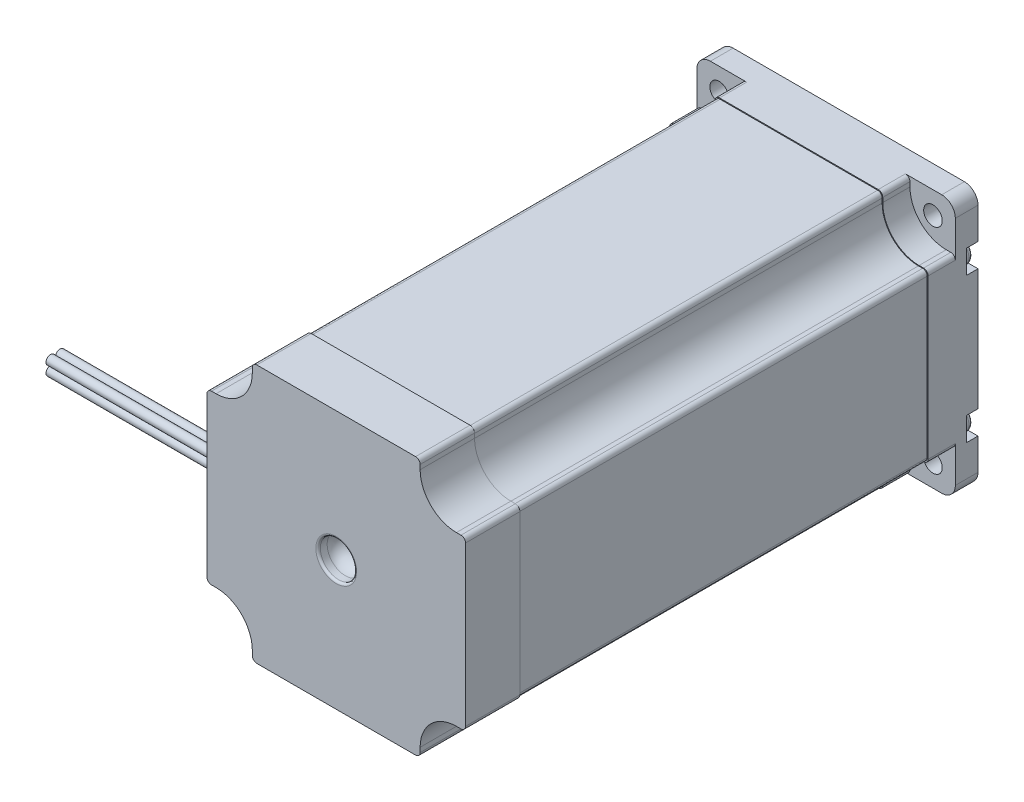
SolidWorks part; units mm, degrees
ref_plane "Front Plane" through (0, 0, 0) normal (0, 0, 1) x (1, 0, 0)
ref_plane "Top Plane" through (0, 0, 0) normal (0, 1, 0) x (1, 0, 0)
ref_plane "Right Plane" through (0, 0, 0) normal (1, 0, 0) x (0, 0, -1)
sketch "Sketch1" plane through (0, 0, 0) normal (0, 0, 1) x (1, 0, 0)
  line L0 (-28.5, 57) -> (-28.5, 0) construction
  line L1 (-3, 0) -> (-54, 0)
  line L2 (0, 3) -> (0, 54)
  line L3 (-3, 57) -> (-54, 57)
  line L4 (-57, 3) -> (-57, 54)
  line L5 (-28.5, 0) -> (-57, 28.5) construction
  line L6 (-57, 28.5) -> (0, 28.5) construction
  circle A0 centre (-52.07, 52.07) radius 2.05
  circle A1 centre (-4.93, 52.07) radius 2.05
  circle A2 centre (-4.93, 4.93) radius 2.05
  circle A3 centre (-52.07, 4.93) radius 2.05
  arc A4 (-3, 0) -> (0, 3) centre (-3, 3) ccw
  arc A5 (-57, 3) -> (-54, 0) centre (-54, 3) ccw
  arc A6 (-3, 57) -> (0, 54) centre (-3, 54) cw
  arc A7 (-57, 54) -> (-54, 57) centre (-54, 54) cw
  point P19 (0, 0)
  point P24 (0, 57)
  point P27 (-57, 57)
  dimension "D3" = 47.14
  dimension "D4" = 47.14
  dimension "D5" = 4.1
  dimension "D6" = 3
  dimension "D1" = 57
  dimension "D2" = 57
extrude "Boss-Extrude1" add sketch "Sketch1" along normal blind 113
sketch "Sketch2" plane through (0, 0, 113) normal (0, 0, 1) x (1, 0, 0)
  line L0 (-47, 60.0294) -> (-47, 47)
  line L1 (-47, 47) -> (-64.0408, 47)
  line L2 (-64.0408, 47) -> (-64.0408, 10)
  line L3 (-64.0408, 10) -> (-47, 10)
  line L4 (-47, 10) -> (-47, -4.5394)
  line L5 (-47, -4.5394) -> (-10, -4.5394)
  line L6 (-10, -4.5394) -> (-10, 10)
  line L7 (-10, 10) -> (8.5456, 10)
  line L8 (8.5456, 10) -> (8.5456, 47)
  line L9 (8.5456, 47) -> (-10, 47)
  line L10 (-10, 47) -> (-10, 60.0294)
  line L11 (-10, 60.0294) -> (-47, 60.0294)
  line L12 (-80.8243, 69.6678) -> (-80.8243, -15.5364)
  line L13 (-80.8243, -15.5364) -> (13.1348, -15.5364)
  line L14 (13.1348, -15.5364) -> (13.1348, 68.1044)
  line L15 (13.1348, 68.1044) -> (-80.8243, 69.6678)
  line L16 (-28.5, 57) -> (-28.5, 0) construction
  line L17 (-3, 57) -> (-54, 57) construction
  line L18 (-54, 0) -> (-3, 0) construction
  line L19 (-28.5, 0) -> (-57, 28.5) construction
  line L20 (-57, 54) -> (-57, 3) construction
  line L21 (-57, 28.5) -> (0, 28.5) construction
  line L22 (0, 3) -> (0, 54) construction
  dimension "D1" = 10
  dimension "D2" = 10
  dimension "D3" = 10
  dimension "D4" = 10
extrude "Cut-Extrude1" cut sketch "Sketch2" against normal blind 108 contours L15 L12 L13 L14 | L11 L0 L1 L2 L3 L4 L5 L6 L7 L8 L9 L10
fillet "Fillet1" radius 8 4 edges at (-10, 10, 59) (-47, 10, 59) (-47, 47, 59) (-10, 47, 59)
fillet "Fillet2" radius 1 8 edges at (-57, 47, 59) (-47, 57, 59) (-10, 57, 59) (0, 47, 59) (0, 10, 59) (-10, 0, 59) (-47, 0, 59) (-57, 10, 59)
ref_plane "Plane4" through (0, 0, 101) normal (0, 0, 1) x (1, 0, 0)
sketch "Sketch3" plane through (0, 0, 101) normal (0, 0, 1) x (1, 0, 0)
  line L0 (-45.8671, 56.8) -> (-11.1329, 56.8)
  line L1 (-10.1329, 55.8) -> (-10.1329, 54.8506)
  line L2 (-2.1329, 46.8506) -> (-1.2, 46.8506)
  line L3 (-0.2, 45.8506) -> (-0.2, 11.1822)
  line L4 (-1.2, 10.1822) -> (-2.0826, 10.1822)
  line L5 (-10.0826, 2.1822) -> (-10.0826, 1.2)
  line L6 (-11.0826, 0.2) -> (-45.9174, 0.2)
  line L7 (-28.5, 0) -> (-28.5, 57) construction
  line L8 (-46, 0) -> (-11, 0) construction
  line L9 (-11, 57) -> (-46, 57) construction
  line L10 (0, 11) -> (0, 46) construction
  line L11 (-10, 1) -> (-10, 2) construction
  line L12 (-46.9174, 2.1822) -> (-46.9174, 1.2)
  line L13 (-55.8, 10.1822) -> (-54.9174, 10.1822)
  line L14 (-56.8, 45.8506) -> (-56.8, 11.1822)
  line L15 (-54.8671, 46.8506) -> (-55.8, 46.8506)
  line L16 (-46.8671, 55.8) -> (-46.8671, 54.8506)
  line L18 (-64.6847, 62.0406) -> (11.9413, 62.0406)
  line L19 (-64.6847, 62.0406) -> (-64.6847, -12.0593)
  line L20 (-64.6847, -12.0593) -> (11.9413, -12.0593)
  line L21 (11.9413, 62.0406) -> (11.9413, -12.0593)
  arc A0 (-10.0826, 2.1822) -> (-2.0826, 10.1822) centre (-2.0826, 2.1822) cw
  arc A1 (-10.1329, 54.8506) -> (-2.1329, 46.8506) centre (-2.1329, 54.8506) ccw
  arc A2 (-11.1329, 56.8) -> (-10.1329, 55.8) centre (-11.1329, 55.8) cw
  arc A3 (-1.2, 46.8506) -> (-0.2, 45.8506) centre (-1.2, 45.8506) cw
  arc A4 (-1.2, 10.1822) -> (-0.2, 11.1822) centre (-1.2, 11.1822) ccw
  arc A5 (-11.0826, 0.2) -> (-10.0826, 1.2) centre (-11.0826, 1.2) ccw
  arc A6 (-10, 55) -> (-2, 47) centre (-2, 55) ccw construction
  arc A7 (-2, 10) -> (-10, 2) centre (-2, 2) ccw construction
  arc A8 (-45.9174, 0.2) -> (-46.9174, 1.2) centre (-45.9174, 1.2) cw
  arc A9 (-55.8, 10.1822) -> (-56.8, 11.1822) centre (-55.8, 11.1822) cw
  arc A10 (-55.8, 46.8506) -> (-56.8, 45.8506) centre (-55.8, 45.8506) ccw
  arc A11 (-45.8671, 56.8) -> (-46.8671, 55.8) centre (-45.8671, 55.8) ccw
  arc A12 (-46.8671, 54.8506) -> (-54.8671, 46.8506) centre (-54.8671, 54.8506) cw
  arc A13 (-46.9174, 2.1822) -> (-54.9174, 10.1822) centre (-54.9174, 2.1822) ccw
  point P8 (-28.5, 56.8)
  point P56 (-28.5, 0.2)
  dimension "D1" = 8
  dimension "D2" = 1
  dimension "D5" = 0.2
  dimension "D7" = 0.2
  dimension "D3" = 0.2
  dimension "D4" = 0.2
  dimension "D6" = 0.2
  dimension "D8" = 0.0826
extrude "Cut-Extrude2" cut sketch "Sketch3" against normal blind 90
sketch "Sketch4" plane through (0, 0, 0) normal (0, 0, -1) x (-1, 0, 0)
  line L0 (28.5, 57) -> (28.5, 0) construction
  line L1 (3, 57) -> (54, 57) construction
  line L2 (54, 0) -> (3, 0) construction
  circle A0 centre (28.5, 28.5) radius 19.05
  dimension "D1" = 38.1
extrude "Boss-Extrude2" add sketch "Sketch4" along normal blind 1.6
sketch "Sketch5" plane through (0, 0, -1.6) normal (0, 0, -1) x (-1, 0, 0)
  circle A0 centre (28.5, 28.5) radius 4
  dimension "D1" = 8
extrude "Boss-Extrude3" add sketch "Sketch5" along normal blind 22.4
sketch "Sketch6" plane through (0, 0, -24) normal (0, 0, -1) x (-1, 0, 0)
  line L0 (20.6729, 24.5) -> (38.159, 24.5) construction
  line L1 (21.9219, 34.9968) -> (35.9108, 34.9968)
  line L2 (21.9219, 34.9968) -> (21.9219, 32)
  line L3 (21.9219, 32) -> (35.9108, 32)
  line L4 (35.9108, 34.9968) -> (35.9108, 32)
  line L5 (54, 0) -> (3, 0) construction
  circle A0 centre (28.5, 28.5) radius 4 construction
  dimension "D1" = 7.5
extrude "Cut-Extrude3" cut sketch "Sketch6" against normal blind 20
sketch "Sketch7" plane through (-57, 0, 0) normal (-1, 0, 0) x (0, 0, 1)
  line L0 (113, 28.5) -> (70.7902, 28.5) construction
  line L1 (113, 46) -> (113, 11) construction
  circle A1 centre (105.3906, 29.7507) radius 1
  circle A2 centre (107.4906, 29.7507) radius 1
  circle A3 centre (107.4906, 27.6507) radius 1
  circle A4 centre (105.3906, 27.6507) radius 1
  dimension "D1" = 2.1
  dimension "D2" = 2
  dimension "D5" = 2.1
  dimension "D3" = 2
  dimension "D4" = 2
extrude "Boss-Extrude4" add sketch "Sketch7" along normal blind 40
fillet "Fillet3" radius 0.5 1 edges at (-47.55, 28.5, -1.6)
sketch "Sketch8" plane through (0, 0, 0) normal (0, 0, -1) x (-1, 0, 0)
  line L0 (28.5, 57) -> (28.5, 0) construction
  line L1 (3, 57) -> (54, 57) construction
  line L2 (54, 0) -> (3, 0) construction
  line L3 (28.5, 0) -> (0, 28.5) construction
  line L4 (0, 3) -> (0, 54) construction
  line L5 (0, 28.5) -> (57, 28.5) construction
  line L6 (57, 54) -> (57, 3) construction
  line L7 (3, 47.07) -> (-1.6146, 47.07)
  line L8 (-1.6146, 47.07) -> (-1.6146, 41.87)
  line L9 (-1.6146, 41.87) -> (3, 41.87)
  line L10 (-1.6146, 15.13) -> (3, 15.13)
  line L11 (-1.6146, 9.93) -> (-1.6146, 15.13)
  line L12 (3, 9.93) -> (-1.6146, 9.93)
  line L13 (58.6146, 9.93) -> (58.6146, 15.13)
  line L14 (54, 9.93) -> (58.6146, 9.93)
  line L15 (58.6146, 15.13) -> (54, 15.13)
  line L16 (58.6146, 41.87) -> (54, 41.87)
  line L17 (58.6146, 47.07) -> (58.6146, 41.87)
  line L18 (54, 47.07) -> (58.6146, 47.07)
  arc A0 (3, 41.87) -> (3, 47.07) centre (3, 44.47) ccw
  arc A1 (3, 15.13) -> (3, 9.93) centre (3, 12.53) cw
  arc A2 (54, 15.13) -> (54, 9.93) centre (54, 12.53) ccw
  arc A3 (54, 41.87) -> (54, 47.07) centre (54, 44.47) cw
  circle A4 centre (4.93, 52.07) radius 2.05 construction
  dimension "D1" = 5.2
  dimension "D2" = 3
  dimension "D3" = 5
extrude "Cut-Extrude4" cut sketch "Sketch8" against normal blind 2.5
sketch "Sketch9" plane through (0, 0, 2.5) normal (0, 0, -1) x (-1, 0, 0)
  line L0 (28.5, 57) -> (28.5, 17.6387) construction
  line L1 (3, 57) -> (54, 57) construction
  line L2 (28.5, 17.6387) -> (0, 28.5) construction
  line L3 (0, 15.13) -> (0, 41.87) construction
  line L4 (0, 28.5) -> (41.5102, 28.5) construction
  circle A0 centre (3, 44.47) radius 2.5
  circle A1 centre (54, 44.47) radius 2.5
  circle A2 centre (54, 12.53) radius 2.5
  circle A3 centre (3, 12.53) radius 2.5
  dimension "D1" = 5
extrude "Boss-Extrude5" add sketch "Sketch9" along normal blind 2 separate body
fillet "Fillet4" radius 1 2 edges at (-5.5, 44.47, 0.5) (-5.5, 44.47, 2.5)
fillet "Fillet5" radius 1 2 edges at (-0.5, 12.53, 2.5) (-0.5, 12.53, 0.5)
fillet "Fillet6" radius 1 2 edges at (-56.5, 12.53, 2.5) (-56.5, 12.53, 0.5)
fillet "Fillet7" radius 1 2 edges at (-51.5, 44.47, 2.5) (-51.5, 44.47, 0.5)
sketch "Sketch10" plane through (0, 0, 0.5) normal (0, 0, -1) x (-1, 0, 0)
  line L0 (3, 45.97) -> (3, 42.97) construction
  line L1 (3, 42.97) -> (1.5, 44.47) construction
  line L2 (1.5, 44.47) -> (4.5, 44.47) construction
  line L3 (2.0618, 44.67) -> (2.0618, 44.27)
  line L4 (2.0618, 44.27) -> (2.8, 44.27)
  line L5 (2.8, 44.27) -> (2.8, 43.5005)
  line L6 (2.8, 43.5005) -> (3.2, 43.5005)
  line L7 (3.2, 43.5005) -> (3.2, 44.27)
  line L8 (3.2, 44.27) -> (3.9382, 44.27)
  line L9 (3.9382, 44.27) -> (3.9382, 44.67)
  line L10 (3.9382, 44.67) -> (3.2, 44.67)
  line L11 (2.0618, 44.67) -> (2.8, 44.67)
  line L12 (2.8, 44.67) -> (2.8, 45.4395)
  line L13 (2.8, 45.4395) -> (3.2, 45.4395)
  line L14 (3.2, 45.4395) -> (3.2, 44.67)
  line L15 (28.5, 57) -> (28.5, 14.0488) construction
  line L16 (3, 57) -> (54, 57) construction
  line L17 (28.5, 14.0488) -> (0, 28.5) construction
  line L18 (0, 15.13) -> (0, 41.87) construction
  line L19 (0, 28.5) -> (40.4844, 28.5) construction
  line L20 (54.2, 45.4395) -> (53.8, 45.4395)
  line L21 (54.2, 44.67) -> (54.2, 45.4395)
  line L22 (54.9382, 44.67) -> (54.2, 44.67)
  line L23 (54.9382, 44.67) -> (54.9382, 44.27)
  line L24 (54.9382, 44.27) -> (54.2, 44.27)
  line L25 (54.2, 44.27) -> (54.2, 43.5005)
  line L26 (54.2, 43.5005) -> (53.8, 43.5005)
  line L27 (53.8, 43.5005) -> (53.8, 44.27)
  line L28 (53.8, 44.27) -> (53.0618, 44.27)
  line L29 (53.0618, 44.27) -> (53.0618, 44.67)
  line L30 (53.0618, 44.67) -> (53.8, 44.67)
  line L31 (53.8, 45.4395) -> (53.8, 44.67)
  line L32 (53.8, 11.5605) -> (53.8, 12.33)
  line L33 (53.0618, 12.33) -> (53.8, 12.33)
  line L34 (53.0618, 12.73) -> (53.0618, 12.33)
  line L35 (53.8, 12.73) -> (53.0618, 12.73)
  line L36 (53.8, 13.4995) -> (53.8, 12.73)
  line L37 (54.2, 13.4995) -> (53.8, 13.4995)
  line L38 (54.2, 12.73) -> (54.2, 13.4995)
  line L39 (54.9382, 12.73) -> (54.2, 12.73)
  line L40 (54.9382, 12.33) -> (54.9382, 12.73)
  line L41 (54.9382, 12.33) -> (54.2, 12.33)
  line L42 (54.2, 12.33) -> (54.2, 11.5605)
  line L43 (54.2, 11.5605) -> (53.8, 11.5605)
  line L44 (1.5, 12.53) -> (4.5, 12.53) construction
  line L45 (3, 14.03) -> (1.5, 12.53) construction
  line L46 (3, 11.03) -> (3, 14.03) construction
  line L47 (3.2, 11.5605) -> (3.2, 12.33)
  line L48 (2.8, 11.5605) -> (3.2, 11.5605)
  line L49 (2.8, 12.33) -> (2.8, 11.5605)
  line L50 (2.0618, 12.33) -> (2.8, 12.33)
  line L51 (3.9382, 12.33) -> (3.2, 12.33)
  line L52 (3.9382, 12.73) -> (3.9382, 12.33)
  line L53 (3.2, 12.73) -> (3.9382, 12.73)
  line L54 (3.2, 13.4995) -> (3.2, 12.73)
  line L55 (2.8, 13.4995) -> (3.2, 13.4995)
  line L56 (2.8, 12.73) -> (2.8, 13.4995)
  line L57 (2.0618, 12.73) -> (2.8, 12.73)
  line L58 (2.0618, 12.33) -> (2.0618, 12.73)
  circle A0 centre (3, 44.47) radius 1.5 construction
  dimension "D1" = 0.4
  dimension "D2" = 0.4
extrude "Cut-Extrude6" cut sketch "Sketch10" against normal blind 1
sketch "Sketch11" plane through (0, 0, 113) normal (0, 0, 1) x (1, 0, 0)
  line L0 (-28.5, 57) -> (-28.5, 0) construction
  line L1 (-11, 57) -> (-46, 57) construction
  line L2 (-46, 0) -> (-11, 0) construction
  circle A0 centre (-28.5, 28.5) radius 4
  dimension "D1" = 8
extrude "Cut-Extrude7" cut sketch "Sketch11" against normal blind 5
fillet "Fillet8" radius 3 1 edges at (-24.5, 28.5, 108)
fillet "Fillet9" radius 0.5 1 edges at (-24.5, 28.5, 113)
